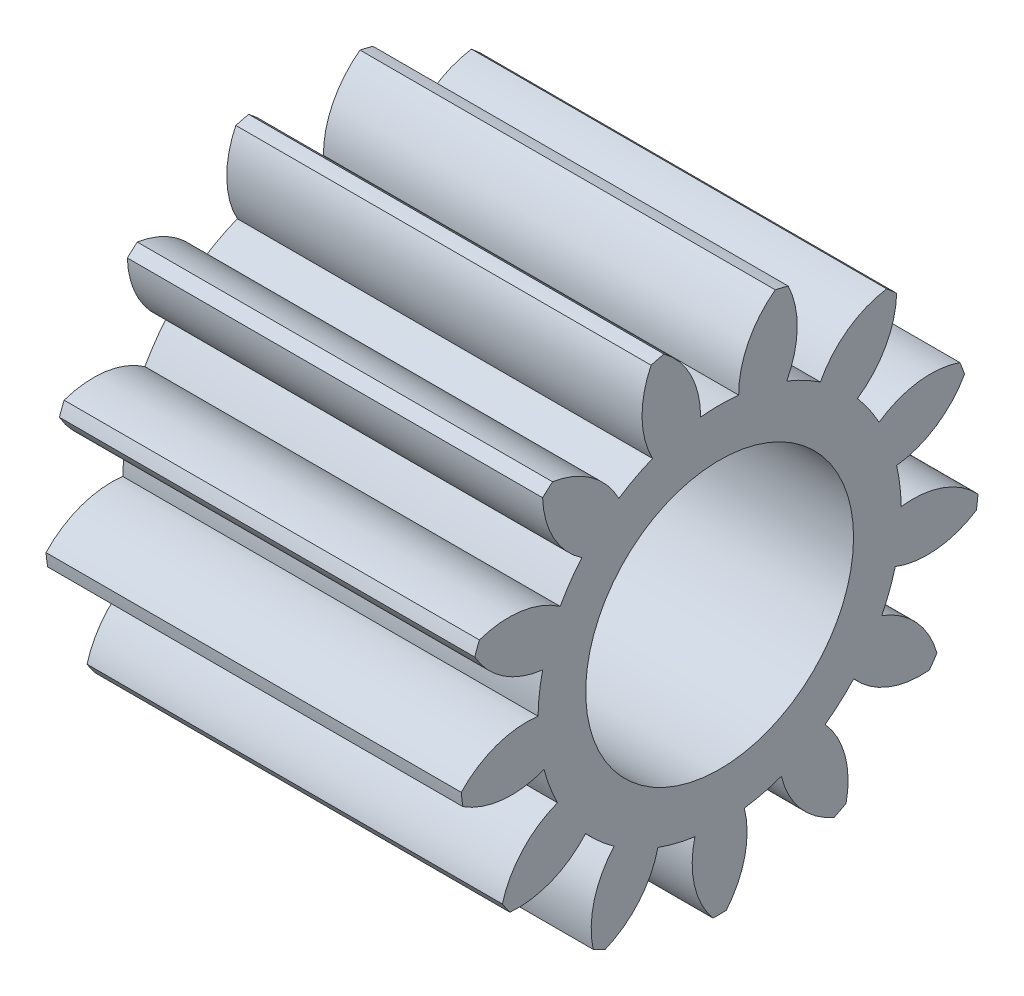
SolidWorks part; units mm, degrees
ref_plane "Plane1" through (0, 0, 0) normal (0, 0, 1) x (1, 0, 0)
ref_plane "Plane2" through (0, 0, 0) normal (0, 1, 0) x (1, 0, 0)
ref_plane "Plane3" through (0, 0, 0) normal (1, 0, 0) x (0, 0, -1)
sketch "HoldingSke" plane through (0, 0, 0) normal (0, 1, 0) x (1, 0, 0)
  line L0 (0, 0) -> (1.9487, -0.4499)
  line L1 (-15, 0) -> (100, 0) construction
  line L2 (0, 0) -> (-2.1039, 2.3779)
  line L3 (0, 0) -> (-11.863, 4.5341)
  line L4 (0, 0) -> (8.4147, 1.9427)
  line L5 (0, 0) -> (-46.8476, -17.4728)
  line L6 (0, 0) -> (-9.9476, -6.7116)
  line L7 (-2.1039, 2.3779) -> (8.6586, 51.2059)
  line L8 (-76.2, 54.61) -> (-76.1, 54.61)
  line L9 (-71.009, 38.7566) -> (-53.1078, 45.2721)
  line L10 (-76.2, 71.12) -> (104.1128, 71.12)
  line L11 (0, 0) -> (-12, 0)
  line L12 (-76.2, 101.6) -> (-76.181, 101.6)
  line L13 (24.9733, 27.94) -> (52.9518, 28.4284)
  line L14 (24.9733, 27.94) -> (24.9743, 27.94)
  line L15 (24.9733, 27.94) -> (100.4006, 29.5858)
  line L16 (-63.627, -0.5) -> (-12.827, -0.5)
  circle A0 centre (0, 0) radius 0.4
  circle A1 centre (0, 0) radius 2.624
  circle A2 centre (0, 0) radius 37.5
  circle A3 centre (0, 0) radius 0.4
  dimension "Num_teeth" = 13
  dimension "Pitch_radius" = 180.3128
  dimension "Width" = 12
sketch "BasProSke" plane through (0, 0, 0) normal (0, 1, 0) x (1, 0, 0)
  line L0 (-10, 0) -> (60, 0) construction
  line L1 (0, 0) -> (0, 3.75)
  line L2 (0, 0) -> (6, 0)
  line L3 (6, 0) -> (6, 3.75)
  line L4 (6, 3.75) -> (0, 3.75)
  dimension "Thickness" = 6
  dimension "Diameter" = 7.5
revolve "Base-Revolve" add sketch "BasProSke" angle 360 about L0
sketch "TooCutSke" plane through (0, 0, 0) normal (1, 0, 0) x (0, 0, -1)
  line L1 (0, 0) -> (0, 107) construction
  line L2 (0, 0) -> (-0.425, 3.2221) construction
  line L3 (0, 0) -> (-1.5461, 6.2726) construction
  line L4 (-0.425, 3.2221) -> (-0.773, 3.1363) construction
  arc A0 (0.2752, 2.6095) -> (-0.2752, 2.6095) centre (0, 0) ccw
  arc A1 (0.8316, 3.6827) -> (-0.8316, 3.6827) centre (0, 0) ccw
  circle A2 centre (0, 0) radius 3.25 construction
  circle A3 centre (0, 0) radius 3.054 construction
  arc A4 (-0.2752, 2.6095) -> (-0.8316, 3.6827) centre (-1.5752, 2.6164) ccw
  arc A5 (0.8316, 3.6827) -> (0.2752, 2.6095) centre (1.5752, 2.6164) ccw
extrude "ToothCut" cut sketch "TooCutSke" along normal through all
fillet "Breaks" [suppressed] radius 0.01 tangent propagation no
fillet "RootFillets" [suppressed] radius 0.126
pattern_circular "TeethCuts" count 13 every 27.692 about axis through (-10, 0, 0) along (1, 0, 0) of "ToothCut", "RootFillets", "Breaks"
sketch "HubNeaOneSke" plane through (0, 0, 0) normal (-1, 0, 0) x (0, 0, 1)
  circle A0 centre (0, 0) radius 2.624
  dimension "Diameter" = 5.248
extrude "HubNearOne" [suppressed] add sketch "HubNeaOneSke" along normal blind 44.0001
sketch "HubNeaBotSke" plane through (0, 0, 0) normal (-1, 0, 0) x (0, 0, 1)
  circle A0 centre (0, 0) radius 2.624
  dimension "Diameter" = 5.248
extrude "HubNearBoth" [suppressed] add sketch "HubNeaBotSke" along normal blind 22
ref_plane "FarPln" through (6, 0, 0) normal (1, 0, 0) x (0, 0, -1)
sketch "HubFarSke" plane through (6, 0, 0) normal (1, 0, 0) x (0, 0, -1)
  circle A0 centre (0, 0) radius 2.624
  dimension "Diameter" = 5.248
extrude "HubFar" [suppressed] add sketch "HubFarSke" along normal blind 22
sketch "BorSke" plane through (0, 0, 0) normal (1, 0, 0) x (0, 0, -1)
  circle A0 centre (0, 0) radius 0.4
  dimension "Diameter" = 0.8
extrude "Bore" cut sketch "BorSke" along normal mid plane 100.0001
sketch "KeySke" plane through (0, 0, 0) normal (1, 0, 0) x (0, 0, -1)
  line L0 (-0.05, 0) -> (-0.05, 0.5)
  line L1 (-0.05, 0.5) -> (0.05, 0.5)
  line L2 (0.05, 0.5) -> (0.05, 0)
  line L3 (0, 0) -> (0, 34) construction
  line L4 (-0.05, 0) -> (0.05, 0)
  dimension "Width" = 0.1
extrude "Keyway" [suppressed] cut sketch "KeySke" along normal mid plane 100.0001
pattern_circular "Keyway2" [suppressed] count 2 every 90 about axis through (-10, 0, 0) along (1, 0, 0) reverse direction yes
sketch "Sketch1" plane through (0, 0, 0) normal (-1, 0, 0) x (0, 0, 1)
  circle A0 centre (0, 0) radius 3
  dimension "D1" = 6
sketch "Sketch3" plane through (0, 0, 0) normal (-1, 0, 0) x (0, 0, 1)
  circle A0 centre (0, 0) radius 3.75
extrude "Boss-Extrude3" [suppressed] add sketch "Sketch3" along normal blind 15
sketch "Sketch4" [suppressed] plane through (-15, 0, 0) normal (-1, 0, 0) x (0, 0, 1)
  line L1 (-2.5, 2.5) -> (2.5, 2.5)
  line L2 (-2.5, 2.5) -> (-2.5, -2.5)
  line L3 (-2.5, -2.5) -> (2.5, -2.5)
  line L4 (2.5, 2.5) -> (2.5, -2.5)
  line L5 (-2.5, 2.5) -> (2.5, -2.5) construction
  line L6 (-2.5, -2.5) -> (2.5, 2.5) construction
  point P0 (0, 0)
  dimension "D1" = 5
  dimension "D2" = 5
extrude "Boss-Extrude4" [suppressed] add sketch "Sketch4" along normal blind 10
sketch "Sketch5" plane through (6, 0, 0) normal (1, 0, 0) x (0, 0, -1)
  circle A0 centre (0, 0) radius 3.75
extrude "Boss-Extrude5" [suppressed] add sketch "Sketch5" along normal blind 15
sketch "Sketch6" plane through (6, 0, 0) normal (1, 0, 0) x (0, 0, -1)
  circle A0 centre (0, 0) radius 1.935
  dimension "D1" = 3.87
extrude "Cut-Extrude1" cut sketch "Sketch6" against normal blind 5
equation "' \"Module@HoldingSke\" = 6.35"
equation "' \"Num_teeth@HoldingSke\" = 12"
equation "' \"Ap@HoldingSke\" =  20"
equation "' \"Ap@HoldingSke\" = 20"
equation "' \"Width@HoldingSke\" = 0.5 * 25.4"
equation "' \"Hub_dia@HoldingSke\"= 1 * 25.4"
equation "' \"Hub_dia@HoldingSke\" = 1 * 25.4"
equation "' \"Overall_len@HoldingSke\" = 1.0 * 25.4"
equation "' \"Bore@HoldingSke\" = 0.75 * 25.4"
equation "' \"T_dim@HoldingSke\" = 0.1 * 25.4"
equation "' \"Width@KeySke\" = 0.25 * 25.4"
equation "' \"Show_teeth@HoldingSke\" = 13"
equation "' \"Backlash@HoldingSke\" = 0.009 * 25.4"
equation "' \"Addendum_fac@HoldingSke\" = 1.0"
equation "' \"Dedendum_fac@HoldingSke\" = 1.25"
equation "' \"Dedendum_add@HoldingSke\" = 0.00005 * 25.4"
equation "' \"Clearance_fac@HoldingSke\" = 0.25"
equation "\"Pitch@HoldingSke\" = 1 / \"Module@HoldingSke\""
equation "\"Overcut_dia@TooCutSke\" = (\"Num_teeth@HoldingSke\" + 2 * \"Addendum_fac@HoldingSke\") / \"Pitch@HoldingSke\" + 0.002 * 25.4"
equation "\"Pitch_dia@TooCutSke\" = \"Num_teeth@HoldingSke\" / \"Pitch@HoldingSke\""
equation "\"Base_dia@TooCutSke\" = \"Num_teeth@HoldingSke\" / \"Pitch@HoldingSke\" * cos((\"Ap@HoldingSke\"  * 3.14159265 / 180))"
equation "\"Root_dia@TooCutSke\" = (\"Num_teeth@HoldingSke\" + 2) / \"Pitch@HoldingSke\" - 2 * (\"Addendum_fac@HoldingSke\" + \"Dedendum_fac@HoldingSke\") / \"Pitch@HoldingSke\" - \"Dedendum_add@HoldingSke\" * 2"
equation "\"Half_ang@TooCutSke\" = 180 / \"Num_teeth@HoldingSke\""
equation "\"Half_CT@TooCutSke\" = \"Num_teeth@HoldingSke\" / \"Pitch@HoldingSke\" * sin((3.14159265 / 2 / \"Num_teeth@HoldingSke\")) / 2 - 7 * \"Backlash@HoldingSke\" / 4"
equation "\"Flank_rad@TooCutSke\" = \"Num_teeth@HoldingSke\" / \"Pitch@HoldingSke\" / 5"
equation "\"Radius@RootFillets\" = \"Clearance_fac@HoldingSke\" / \"Pitch@HoldingSke\" + \"Dedendum_add@HoldingSke\""
equation "\"Break_rad@Breaks\" = 0.02 / \"Pitch@HoldingSke\""
equation "\"Thickness@HoldingSke\" = \"Width@HoldingSke\""
equation "\"OAL@HoldingSke\" = \"Thickness@HoldingSke\""
equation "\"MHD@HoldingSke\" = (\"Num_teeth@HoldingSke\" + 2) / \"Pitch@HoldingSke\" - 2 * (\"Addendum_fac@HoldingSke\" + \"Dedendum_fac@HoldingSke\")  / \"Pitch@HoldingSke\" - \"Dedendum_add@HoldingSke\" * 2"
equation "\"MBD@HoldingSke\" = (\"Num_teeth@HoldingSke\" + 2) / \"Pitch@HoldingSke\" - 2 * (\"Addendum_fac@HoldingSke\" + \"Dedendum_fac@HoldingSke\")  / \"Pitch@HoldingSke\" - \"Dedendum_add@HoldingSke\" * 2 - 0.002 * 25.4"
equation "\"MHD@HoldingSke\" = ((sgn( \"MHD@HoldingSke\" - \"Hub_dia@HoldingSke\" )-1)*( \"MHD@HoldingSke\" - \"Hub_dia@HoldingSke\" ))/-2+ \"Hub_dia@HoldingSke\""
equation "\"MBD@HoldingSke\" = ((sgn( \"MBD@HoldingSke\" - \"Bore@HoldingSke\" )-1)*( \"MBD@HoldingSke\" - \"Bore@HoldingSke\" ))/-2+ \"Bore@HoldingSke\""
equation "\"OAL@HoldingSke\" = ((sgn( \"OAL@HoldingSke\" - \"Overall_len@HoldingSke\" )+1)*( \"OAL@HoldingSke\" - \"Overall_len@HoldingSke\" ))/2 + \"Overall_len@HoldingSke\" + 0.000002 * 25.4"
equation "\"Num_teeth@TeethCuts\" = int( \"Show_teeth@HoldingSke\" ) + 1"
equation "\"Num_teeth@TeethCuts\" = ((sgn( \"Num_teeth@TeethCuts\" - \"Num_teeth@HoldingSke\" )-1)*( \"Num_teeth@TeethCuts\" - \"Num_teeth@HoldingSke\" ))/-2+ \"Num_teeth@HoldingSke\""
equation "\"Num_teeth@TeethCuts\" = ((sgn( \"Num_teeth@TeethCuts\" - 2.0)+1)*( \"Num_teeth@TeethCuts\" - 2.0))/2 +2.0"
equation "\"Angle@TeethCuts\" = 360.0 / \"Num_teeth@HoldingSke\""
equation "\"Diameter@BasProSke\" = (\"Num_teeth@HoldingSke\" + 2 * \"Addendum_fac@HoldingSke\") / \"Pitch@HoldingSke\""
equation "\"Thickness@BasProSke\"=6"
equation "' \"Fillet_rad@BasProSke\" =  \"Thickness@HoldingSke\" * 0.05"
equation "' \"Fillet_rad@BasProSke\" = \"Thickness@HoldingSke\" * 0.05"
equation "\"MHD@HoldingSke\" = ((sgn( \"MHD@HoldingSke\" - \"Root_dia@TooCutSke\" )-1)*( \"MHD@HoldingSke\" - \"Root_dia@TooCutSke\" ))/-2+ \"Root_dia@TooCutSke\""
equation "\"Diameter@HubNeaOneSke\" = \"MHD@HoldingSke\""
equation "\"Length@HubNearOne\" = \"OAL@HoldingSke\" - \"Thickness@BasProSke\""
equation "\"Diameter@HubNeaBotSke\" = \"MHD@HoldingSke\""
equation "\"Length@HubNearBoth\" = ( \"OAL@HoldingSke\" - \"Thickness@BasProSke\" ) / 2.0"
equation "\"Thickness@FarPln\" = \"Thickness@BasProSke\""
equation "\"Diameter@HubFarSke\" = \"MHD@HoldingSke\""
equation "\"Length@HubFar\" = ( \"OAL@HoldingSke\" - \"Thickness@BasProSke\" ) / 2.0"
equation "\"Diameter@BorSke\" = \"MBD@HoldingSke\""
equation "\"D1@Bore\" = \"OAL@HoldingSke\" * 2.0"
equation "\"D1@Keyway\" = \"OAL@HoldingSke\" * 2.0"
equation "\"Offset@KeySke\" = \"T_dim@HoldingSke\" + \"MBD@HoldingSke\" / 2.0"
